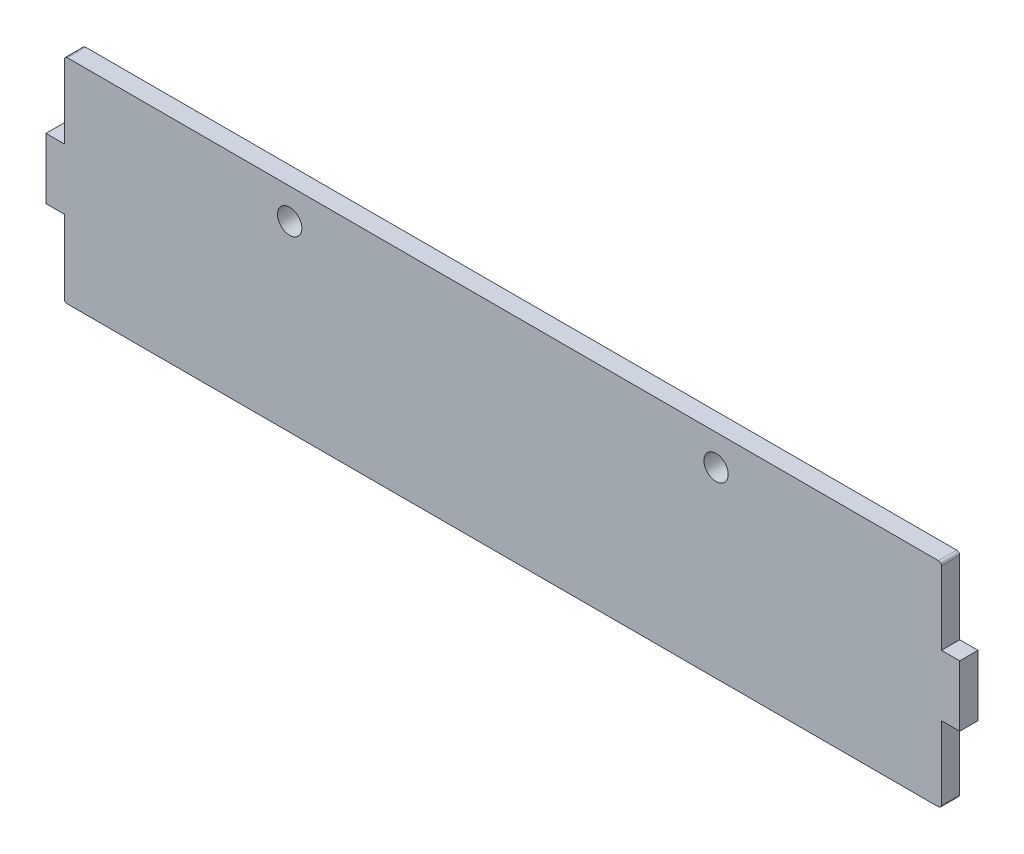
SolidWorks part; units mm, degrees
material "Beech"
ref_plane "Спереди" through (0, 0, 0) normal (0, 0, 1) x (1, 0, 0)
ref_plane "Сверху" through (0, 0, 0) normal (0, 1, 0) x (1, 0, 0)
ref_plane "Справа" through (0, 0, 0) normal (1, 0, 0) x (0, 0, -1)
sketch "Sketch1" plane through (0, 0, 0) normal (0, 0, 1) x (1, 0, 0)
  line L1 (0, 0) -> (300, 0)
  line L2 (0, 0) -> (0, 70)
  line L3 (0, 70) -> (300, 70)
  line L4 (300, 0) -> (300, 70)
  dimension "D1" = 70
  dimension "D2" = 300
extrude "front" add sketch "Sketch1" against normal blind 6
sketch "Sketch2" plane through (0, 0, 0) normal (0, 0, 1) x (1, 0, 0)
  line L0 (6, 70) -> (6, 45)
  line L1 (300, 70) -> (0, 70) construction
  line L2 (6, 45) -> (0, 45)
  line L3 (0, 70) -> (0, 0) construction
  line L4 (0, 25) -> (6, 25)
  line L5 (6, 25) -> (6, 0)
  line L6 (0, 0) -> (300, 0) construction
  line L7 (0, 45) -> (0, 25)
  line L8 (6, 70) -> (0, 70)
  line L9 (0, 70) -> (0, 45)
  line L10 (80, 60) -> (220, 60) construction
  line L11 (0, 25) -> (0, 0)
  line L12 (0, 0) -> (6, 0)
  line L13 (294, 70) -> (294, 45)
  line L14 (294, 45) -> (300, 45)
  line L15 (300, 0) -> (300, 70) construction
  line L16 (300, 45) -> (300, 70)
  line L17 (300, 70) -> (294, 70)
  line L18 (300, 25) -> (294, 25)
  line L19 (294, 25) -> (294, 0)
  line L20 (294, 0) -> (300, 0)
  line L21 (300, 0) -> (300, 25)
  circle A0 centre (80, 60) radius 4
  circle A1 centre (220, 60) radius 4
  point P32 (150, 70)
  point P33 (150, 60)
  line M1 (0, 70) -> (0, 0)
  line M2 (0, 0) -> (300, 0)
  line M4 (300, 70) -> (0, 70)
  dimension "D4" = 8
  dimension "D1" = 6
  dimension "D2" = 20
  dimension "D3" = 140
  dimension "D5" = 10
extrude "mount" cut sketch "Sketch2" against normal through all contours L2 L0 M4 M1 | L5 L4 M1 M2 | L16 L17 L13 L14 | L21 L18 L19 L20 | A0 | A1 region at (3, 12.5, 0) region at (3, 57.5, 0)
fillet "fillet" radius 1 4 edges at (294, 0, -3) (294, 70, -3) (6, 0, -3) (6, 70, -3)
